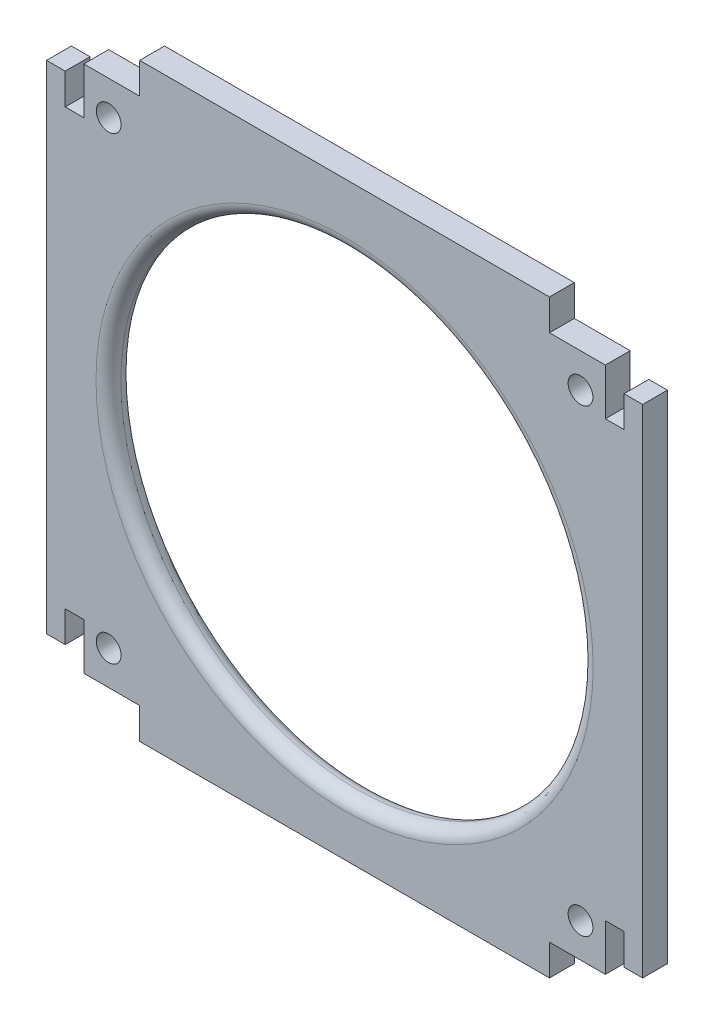
SolidWorks part; units mm, degrees
material "6061-T6 (SS)"
ref_plane "Front Plane" through (0, 0, 0) normal (0, 0, 1) x (1, 0, 0)
ref_plane "Top Plane" through (0, 0, 0) normal (0, 1, 0) x (1, 0, 0)
ref_plane "Right Plane" through (0, 0, 0) normal (1, 0, 0) x (0, 0, -1)
sketch "Sketch1" plane through (0, 0, 0) normal (0, 0, 1) x (1, 0, 0)
  line L0 (0, 0) -> (9, 0)
  line L5 (9, 0) -> (9, 5)
  line L6 (9, 5) -> (75, 5)
  line L7 (75, 5) -> (75, 0)
  line L8 (75, 0) -> (84, 0)
  line L9 (0, -85) -> (9, -85)
  line L10 (9, -85) -> (9, -90)
  line L11 (9, -90) -> (75, -90)
  line L12 (75, -90) -> (75, -85)
  line L13 (75, -85) -> (84, -85)
  line L17 (-3, -2.5) -> (-6, -2.5)
  line L18 (-6, -2.5) -> (-6, -82.5)
  line L19 (-6, -82.5) -> (-3, -82.5)
  line L26 (87, -2.5) -> (90, -2.5)
  line L27 (90, -2.5) -> (90, -82.5)
  line L28 (90, -82.5) -> (87, -82.5)
  line L32 (-3, -7.5) -> (0, -7.5)
  line L33 (-3, -2.5) -> (-3, -7.5)
  line L34 (0, 0) -> (0, -7.5)
  line L35 (84, 0) -> (84, -7.5)
  line L36 (84, -7.5) -> (87, -7.5)
  line L37 (87, -7.5) -> (87, -2.5)
  line L38 (-3, -82.5) -> (-3, -77.5)
  line L39 (-3, -77.5) -> (0, -77.5)
  line L40 (0, -77.5) -> (0, -85)
  line L41 (84, -85) -> (84, -77.5)
  line L42 (84, -77.5) -> (87, -77.5)
  line L43 (87, -77.5) -> (87, -82.5)
  circle A4 centre (4, -5.5) radius 2
  circle A5 centre (80, -5.4999) radius 2
  circle A6 centre (80, -79.5) radius 2
  circle A7 centre (4, -79.5001) radius 2
  circle A8 centre (42, -43.1556) radius 38.0335
extrude "Boss-Extrude1" add sketch "Sketch1" along normal blind 4
fillet "Fillet1" radius 2 2 edges at (80.0335, -43.1556, 4) (80.0335, -43.1556, 0)
